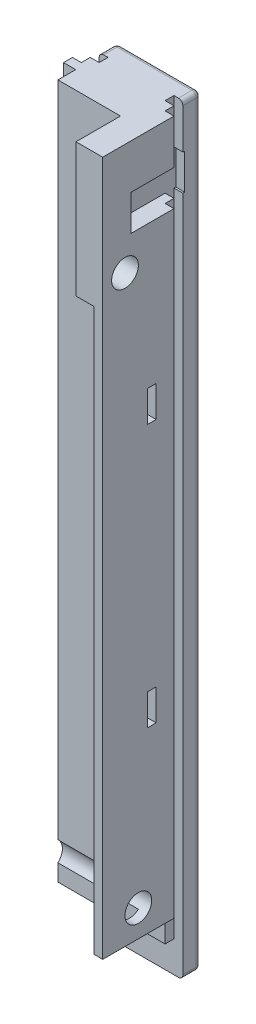
SolidWorks part; units mm, degrees
ref_plane "Front Plane" through (0, 0, 0) normal (0, 0, 1) x (1, 0, 0)
ref_plane "Top Plane" through (0, 0, 0) normal (0, 1, 0) x (1, 0, 0)
ref_plane "Right Plane" through (0, 0, 0) normal (1, 0, 0) x (0, 0, -1)
sketch "Sketch1" plane through (0, 0, 0) normal (0, 1, 0) x (1, 0, 0)
  line L0 (-3.4214, 1.8186) -> (-3.4214, 0.8186)
  line L1 (-4.4214, 3.8186) -> (4.9786, 3.8186)
  line L2 (-4.4214, 3.8186) -> (-4.4214, 1.8186)
  line L3 (-4.4214, 1.8186) -> (4.9786, 1.8186)
  line L4 (4.9786, 3.8186) -> (4.9786, 1.8186)
  line L5 (-3.4214, 0.8186) -> (-4.4214, 0.8186)
  line L6 (-4.4214, 0.8186) -> (-4.4214, -0.1814)
  line L7 (-4.4214, -0.1814) -> (4.9786, -0.1814)
  line L8 (4.9786, -0.1814) -> (4.9786, 0.8186)
  line L9 (4.9786, 0.8186) -> (3.9786, 0.8186)
  line L10 (3.9786, 0.8186) -> (3.9786, 1.8186)
  line L11 (4.9786, -0.1814) -> (5.9786, -0.1814)
  line L12 (5.9786, -0.1814) -> (5.9786, -8.1814)
  line L13 (5.9786, -8.1814) -> (2.9786, -8.1814)
  line L14 (2.9786, -8.1814) -> (2.9786, -3.1814)
  line L15 (2.9786, -3.1814) -> (-4.051, -3.1814)
  line L16 (-4.051, -3.1814) -> (-4.051, -1.1814)
  line L17 (-4.051, -1.1814) -> (-5.4214, -1.1814)
  line L18 (-5.4214, -1.1814) -> (-5.4214, -0.1814)
  line L19 (-5.4214, -0.1814) -> (-4.4214, -0.1814)
  dimension "D1" = 9.4
  dimension "D2" = 2
  dimension "D3" = 1
  dimension "D4" = 1
  dimension "D5" = 1
  dimension "D6" = 1
  dimension "D7" = 1
  dimension "D8" = 1
  dimension "D9" = 1
  dimension "D10" = 1
  dimension "D11" = 1
  dimension "D12" = 8
  dimension "D13" = 3
  dimension "D14" = 3
extrude "Boss-Extrude1" add sketch "Sketch1" against normal blind 85.5 contours L4 L1 L2 L3 region at (0.2786, 0, -2.8186)
extrude "Boss-Extrude2" add sketch "Sketch1<3>" against normal blind 81 contours L9 L10 L3 L0 L5 L6 L7 L8 region at (0.2786, 0, -0.7591)
sketch "Sketch1<3>" plane through (0, 0, 0) normal (0, 1, 0) x (1, 0, 0) same geometry as "Sketch1"
fillet "Fillet1" radius 0.5 8 edges at (-4.4214, -85.5, -2.8186) (4.9786, -85.5, -2.8186) (0.2786, -85.5, -3.8186) (-4.4214, 0, -2.8186) (4.9786, 0, -2.8186) (0.2786, 0, -3.8186) (4.9786, -42.75, -3.8186) (-4.4214, -42.75, -3.8186)
extrude "Boss-Extrude3" add sketch "Sketch1<4>" against normal blind 78 contours L19 L18 L17 L16 L15 L14 L13 L12 L11 L7 region at (1.9304, 0, 2.9434)
sketch "Sketch1<4>" plane through (0, 0, 0) normal (0, 1, 0) x (1, 0, 0) same geometry as "Sketch1"
sketch "Sketch2" plane through (5.9786, 0, 0) normal (1, 0, 0) x (0, 0, -1)
  line L0 (-0.1814, 0) -> (-8.1814, 0) construction
  line L1 (-0.1814, -78) -> (-8.1814, -78) construction
  line L3 (-0.1814, -78) -> (-0.1814, 0) construction
  line L4 (1.8186, -81) -> (1.8186, 0) construction
  line L5 (-4.9814, -5) -> (2.0186, -5)
  line L6 (-4.9814, -5) -> (-4.9814, -9)
  line L7 (-4.9814, -9) -> (2.0186, -9)
  line L8 (2.0186, -5) -> (2.0186, -9)
  circle A0 centre (-5.6814, -12.5) radius 1.5
  circle A1 centre (-4.1814, -75) radius 1.5
  line M6 (-0.1814, -78) -> (-0.1814, 0)
  dimension "D1" = 3
  dimension "D2" = 3
  dimension "D3" = 12.5
  dimension "D4" = 3
  dimension "D5" = 4
  dimension "D6" = 5.5
  dimension "D7" = 5
  dimension "D8" = 4
  dimension "D9" = 7
  dimension "D10" = 0.2
extrude "Cut-Extrude1" cut sketch "Sketch2" against normal through all contours A0 | A1 region at (5.9786, -12.5, 5.6814) region at (5.9786, -75, 4.1814)
extrude "Cut-Extrude2" cut sketch "Sketch2<3>" against normal up to surface (2 mm away) contours L6 L7 L5 M6 | L8 L5 L7 M6 region at (5.9786, -7, 2.5814) region at (5.9786, -7, -0.9186) up to face at (3.9786, -40.5, -1.3186)
sketch "Sketch2<3>" plane through (5.9786, 0, 0) normal (1, 0, 0) x (0, 0, -1) same geometry as "Sketch2"
sketch "Sketch3" plane through (0, 0, 8.1814) normal (0, 0, 1) x (1, 0, 0)
  line L0 (2.9786, -78) -> (2.9786, 0) construction
  line L1 (2.9786, -15) -> (4.9786, -15)
  line L2 (2.9786, -15) -> (2.9786, -78)
  line L3 (2.9786, -78) -> (4.9786, -78)
  line L4 (4.9786, -15) -> (4.9786, -78)
  line L6 (5.9786, -78) -> (2.9786, -78) construction
  line L7 (5.9786, 0) -> (2.9786, 0) construction
  line L8 (5.9786, -78) -> (5.9786, 0) construction
  dimension "D1" = 15
  dimension "D2" = 1
extrude "Cut-Extrude3" cut sketch "Sketch3" against normal up to surface (5 mm away) up to face at (-0.5362, -36.941, 3.1814)
sketch "Sketch4" plane through (5.9786, 0, 0) normal (1, 0, 0) x (0, 0, -1)
  line L0 (-0.1814, 0) -> (-8.1814, 0) construction
  line L1 (-2.1814, -28.5) -> (-3.1814, -28.5)
  line L2 (-2.1814, -28.5) -> (-2.1814, -25)
  line L3 (-2.1814, -25) -> (-3.1814, -25)
  line L4 (-3.1814, -28.5) -> (-3.1814, -25)
  line L5 (-2.1814, -58) -> (-3.1814, -58)
  line L6 (-2.1814, -58) -> (-2.1814, -54.5)
  line L7 (-2.1814, -54.5) -> (-3.1814, -54.5)
  line L8 (-3.1814, -58) -> (-3.1814, -54.5)
  line L9 (-0.1814, -78) -> (-0.1814, -9) construction
  line L10 (-0.1814, -78) -> (-0.1814, -9) construction
  line L11 (-0.1814, -78) -> (-8.1814, -78) construction
  point P8 (-2.6814, -25)
  dimension "D1" = 1
  dimension "D2" = 3.5
  dimension "D3" = 1
  dimension "D4" = 3.5
  dimension "D5" = 25
  dimension "D6" = 2
  dimension "D7" = 2
  dimension "D8" = 20
extrude "Cut-Extrude4" cut sketch "Sketch4" against normal blind 2
